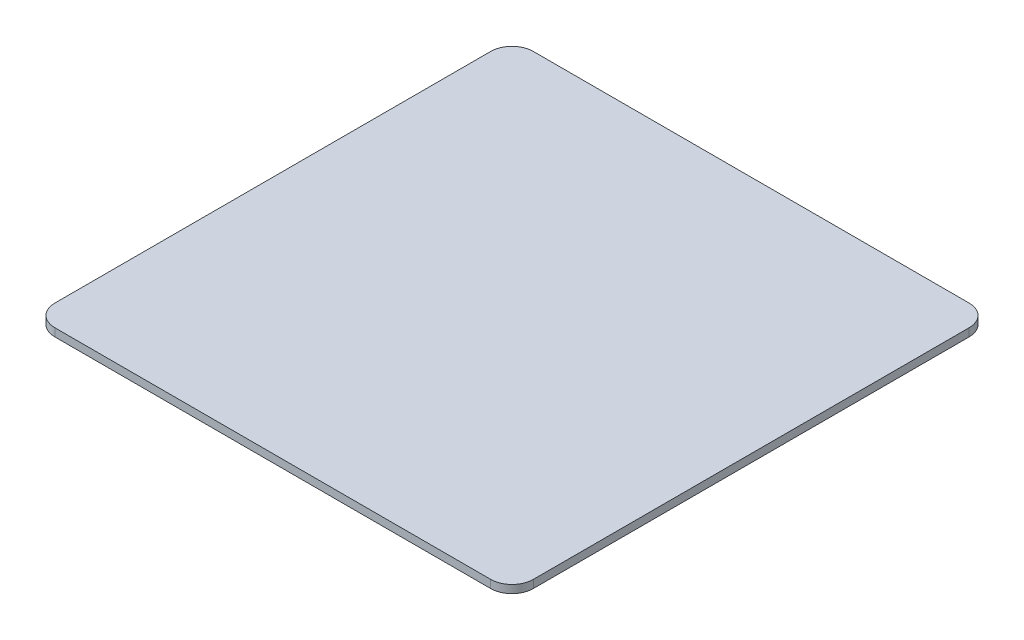
SolidWorks part; units mm, degrees
ref_plane "Plano frontal" through (0, 0, 0) normal (0, 0, 1) x (1, 0, 0)
ref_plane "Plano superior" through (0, 0, 0) normal (0, 1, 0) x (1, 0, 0)
ref_plane "Plano direito" through (0, 0, 0) normal (1, 0, 0) x (0, 0, -1)
sketch "Esboço1" plane through (0, 0, 0) normal (0, 1, 0) x (1, 0, 0)
  line L1 (82, -90) -> (-82, -90)
  line L2 (90, -82) -> (90, 82)
  line L3 (82, 90) -> (-82, 90)
  line L4 (-90, -82) -> (-90, 82)
  line L5 (90, -90) -> (-90, 90) construction
  line L6 (90, 90) -> (-90, -90) construction
  arc A0 (82, -90) -> (90, -82) centre (82, -82) ccw
  arc A1 (-82, -90) -> (-90, -82) centre (-82, -82) cw
  arc A2 (90, 82) -> (82, 90) centre (82, 82) ccw
  arc A3 (-82, 90) -> (-90, 82) centre (-82, 82) ccw
  point P0 (0, 0)
  dimension "D3" = 8
  dimension "D1" = 180
  dimension "D2" = 180
extrude "Ressalto-extrusão1" add sketch "Esboço1" along normal blind 3
sketch "Esboço2" plane through (0, 0, 0) normal (0, -1, 0) x (-1, 0, 0)
  line L0 (82, -90) -> (-82, -90) construction
  line L1 (90, 82) -> (90, -82) construction
  line L2 (0, 0) -> (-90, 0) construction
  line L3 (-90, -82) -> (-90, 82) construction
  line L4 (0, 0) -> (0, -90) construction
  circle A0 centre (79, -62) radius 3.5
  circle A1 centre (-79, -62) radius 3.5
  circle A2 centre (-79, 62) radius 3.5
  circle A3 centre (79, 62) radius 3.5
  dimension "D1" = 7
  dimension "D2" = 28
  dimension "D3" = 11
extrude "Ressalto-extrusão2" add sketch "Esboço2" along normal blind 5
